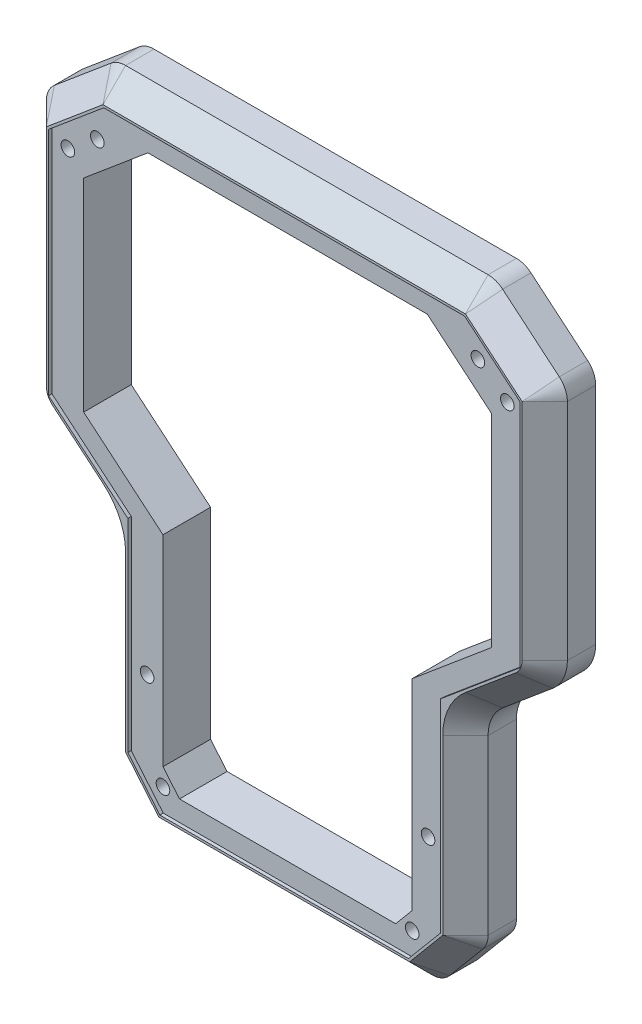
SolidWorks part; units mm, degrees
ref_plane "Plano frontal" through (0, 0, 0) normal (0, 0, 1) x (1, 0, 0)
ref_plane "Plano superior" through (0, 0, 0) normal (0, 1, 0) x (1, 0, 0)
ref_plane "Plano direito" through (0, 0, 0) normal (1, 0, 0) x (0, 0, -1)
sketch "Esboço1" plane through (0, 0, 0) normal (0, 0, 1) x (1, 0, 0)
  line L0 (-55.3369, 0) -> (55.3369, 0)
  line L1 (-80, 27.4748) -> (-80, 103.8351)
  line L2 (-86.4279, 117.6197) -> (-108.5721, 136.2009)
  line L3 (-115, 149.9856) -> (-115, 249.0225)
  line L4 (-80, 280) -> (80, 280)
  line L5 (0, 280) -> (0, 0) construction
  line L6 (-86.4279, 277.6604) -> (-111.4279, 256.683)
  line L7 (-90, 146.7252) -> (-90, 236.2287)
  line L8 (-90, 236.2287) -> (-61.6704, 260)
  line L9 (47.7197, 20) -> (-47.7197, 20)
  line L10 (-55, 28.6763) -> (-55, 117.3567)
  line L11 (-55, 117.3567) -> (-90, 146.7252)
  line L12 (-77.6604, 21.0469) -> (-62.9974, 3.5721)
  line L13 (-55, 28.6763) -> (-47.7197, 20)
  line L14 (-61.6704, 260) -> (61.6704, 260)
  line L15 (55, 28.6763) -> (47.7197, 20)
  line L16 (77.6604, 21.0469) -> (62.9974, 3.5721)
  line L17 (55, 117.3567) -> (90, 146.7252)
  line L18 (55, 28.6763) -> (55, 117.3567)
  line L19 (90, 236.2287) -> (61.6704, 260)
  line L20 (90, 146.7252) -> (90, 236.2287)
  line L21 (86.4279, 277.6604) -> (111.4279, 256.683)
  line L22 (115, 149.9856) -> (115, 249.0225)
  line L23 (86.4279, 117.6197) -> (108.5721, 136.2009)
  line L24 (80, 27.4748) -> (80, 103.8351)
  arc A0 (-115, 249.0225) -> (-111.4279, 256.683) centre (-105, 249.0225) cw
  arc A1 (-108.5721, 136.2009) -> (-115, 149.9856) centre (-97.0055, 149.9856) cw
  arc A2 (-80, 103.8351) -> (-86.4279, 117.6197) centre (-97.9945, 103.8351) ccw
  arc A3 (80, 280) -> (86.4279, 277.6604) centre (80, 270) cw
  arc A4 (-80, 280) -> (-86.4279, 277.6604) centre (-80, 270) ccw
  arc A5 (80, 103.8351) -> (86.4279, 117.6197) centre (97.9945, 103.8351) cw
  arc A6 (108.5721, 136.2009) -> (115, 149.9856) centre (97.0055, 149.9856) ccw
  arc A7 (115, 249.0225) -> (111.4279, 256.683) centre (105, 249.0225) ccw
  arc A8 (77.6604, 21.0469) -> (80, 27.4748) centre (70, 27.4748) ccw
  arc A9 (62.9974, 3.5721) -> (55.3369, 0) centre (55.3369, 10) cw
  arc A10 (-55.3369, 0) -> (-62.9974, 3.5721) centre (-55.3369, 10) cw
  arc A11 (-80, 27.4748) -> (-77.6604, 21.0469) centre (-70, 27.4748) ccw
  point P27 (-115, 253.6856)
  point P33 (0, 20)
  point P40 (0, 260)
  point P46 (0, 20)
  point P47 (115, 253.6856)
  point P50 (80, 23.8351)
  point P53 (0, 280)
  point P54 (60, 0)
  point P57 (-60, 0)
  point P60 (-80, 23.8351)
  dimension "D7" = 50
  dimension "D12" = 10
  dimension "D14" = 10
  dimension "D19" = 10
  dimension "D2" = 115
  dimension "D3" = 280
  dimension "D4" = 80
  dimension "D5" = 80
  dimension "D6" = 50
  dimension "D8" = 20
  dimension "D9" = 20
  dimension "D10" = 25
  dimension "D11" = 20
  dimension "D13" = 50
  dimension "D15" = 25
  dimension "D16" = 50
  dimension "D17" = 60
  dimension "D18" = 50
extrude "Ressalto-extrusão1" add sketch "Esboço1" along normal mid plane 45 contours L5 L4 L6 L3 A1 L2 A2 L1 L12 L0 L10 L11 L14 | L4 L5 L14 L0 region at (-58.2839, 3.6803, 0) region at (3.027, 10, 0)
chamfer "Chanfro1" distance 10 angle 45 48 edges at (0, 0, 22.5) (-70.3289, 12.3095, 22.5) (-80, 65.6549, 22.5) (-81.6859, 111.4399, 22.5) (-97.5, 126.9103, 22.5) (0, 280, 22.5) (-113.3141, 142.3807, 22.5) (-98.9279, 267.1717, 22.5) (-115, 199.504, 22.5) (0, 0, -22.5) (-70.3289, 12.3095, -22.5) (-80, 65.6549, -22.5) (-81.6859, 111.4399, -22.5) (-97.5, 126.9103, -22.5) (0, 280, -22.5) (-113.3141, 142.3807, -22.5) (-98.9279, 267.1717, -22.5) (-115, 199.504, -22.5) (80, 65.6549, 22.5) (81.6859, 111.4399, 22.5) (97.5, 126.9103, 22.5) (113.3141, 142.3807, 22.5) (115, 199.504, 22.5) (114.0631, 253.2487, 22.5) (98.9279, 267.1717, 22.5) (83.4202, 279.3969, 22.5) (-83.4202, 279.3969, 22.5) (-114.0631, 253.2487, 22.5) (80, 65.6549, -22.5) (81.6859, 111.4399, -22.5) (97.5, 126.9103, -22.5) (113.3141, 142.3807, -22.5) (115, 199.504, -22.5) (114.0631, 253.2487, -22.5) (98.9279, 267.1717, -22.5) (83.4202, 279.3969, -22.5) (-83.4202, 279.3969, -22.5) (-114.0631, 253.2487, -22.5) (70.3289, 12.3095, -22.5) (70.3289, 12.3095, 22.5) (79.3969, 24.0546, 22.5) (59.5631, 0.9369, 22.5) (-59.5631, 0.9369, 22.5) (-79.3969, 24.0546, 22.5) (79.3969, 24.0546, -22.5) (59.5631, 0.9369, -22.5) (-59.5631, 0.9369, -22.5) (-79.3969, 24.0546, -22.5)
sketch "Esboço3" plane through (0, 0, 0) normal (0, 0, 1) x (1, 0, 0)
  line L1 (-722.7729, 507.4347) -> (416.458, 507.4347)
  line L2 (-722.7729, 507.4347) -> (-722.7729, -202.3634)
  line L3 (-722.7729, -202.3634) -> (416.458, -202.3634)
  line L4 (416.458, 507.4347) -> (416.458, -202.3634)
extrude "Corte-extrusão1" cut sketch "Esboço3" against normal up to next
sketch "Esboço4" plane through (0, 0, 22.5) normal (0, 0, 1) x (1, 0, 0)
  line L0 (-90, 146.7252) -> (-90, 236.2287)
  line L1 (-55, 117.3567) -> (-90, 146.7252)
  line L2 (-55, 117.3567) -> (-90, 146.7252) construction
  line L3 (-55, 28.6763) -> (-55, 117.3567)
  line L4 (-55, 28.6763) -> (-47.7197, 20)
  line L5 (0, -6.7811) -> (0, 343.2781) construction
  line L6 (-47.7197, 20) -> (47.7197, 20)
  line L7 (55, 28.6763) -> (47.7197, 20)
  line L8 (-69, 27.8387) -> (-54.8706, 11)
  line L9 (-54.8706, 11) -> (54.8706, 11)
  line L10 (90, 236.2287) -> (61.6704, 260) construction
  line L11 (-90, 236.2287) -> (-61.6704, 260)
  line L12 (-61.6704, 260) -> (61.6704, 260)
  line L13 (-104, 248.5562) -> (-79.636, 269)
  line L14 (-104, 248.5562) -> (-104, 146.7239)
  line L15 (-104, 146.7239) -> (-69, 117.3555)
  line L16 (-69, 117.3555) -> (-69, 27.8387)
  line L17 (54.8706, 11) -> (69, 27.8387)
  line L18 (61.6704, 260) -> (90, 236.2287)
  line L19 (-79.636, 269) -> (79.636, 269)
  line L20 (69, 117.3555) -> (69, 27.8387)
  line L21 (104, 146.7239) -> (69, 117.3555)
  line L22 (104, 248.5562) -> (104, 146.7239)
  line L23 (-70, 27.4748) -> (-55.3369, 10) construction
  line L24 (55, 28.6763) -> (55, 117.3567)
  line L25 (55, 117.3567) -> (90, 146.7252)
  line L26 (90, 236.2287) -> (90, 146.7252)
  line L27 (79.636, 269) -> (104, 248.5562)
  line L28 (-80, 270) -> (-105, 249.0225) construction
  line L29 (105, 249.0225) -> (80, 270) construction
  line L30 (55.3369, 10) -> (70, 27.4748) construction
  dimension "D1" = 14
  dimension "D2" = 9
  dimension "D3" = 9
  dimension "D4" = 14
  dimension "D5" = 9
  dimension "D6" = 1
  dimension "D7" = 1
extrude "Corte-extrusão5" cut sketch "Esboço4" against normal blind 1.5
sketch "Esboço5" plane through (0, 0, 21) normal (0, 0, 1) x (1, 0, 0)
  line L1 (-104, 248.5562) -> (-104, 146.7239) construction
  line L2 (-69, 117.3555) -> (-69, 27.8387) construction
  line L3 (0, -34.4878) -> (0, 335.3959) construction
  line L5 (-104, 248.5562) -> (-104, 146.7239) construction
  line L7 (79.636, 269) -> (-79.636, 269) construction
  line L8 (-69, 117.3555) -> (-69, 27.8387) construction
  line L9 (-54.8706, 11) -> (54.8706, 11) construction
  circle A0 centre (-97, 244) radius 3
  circle A1 centre (-62, 60.3962) radius 3
  circle A2 centre (-84, 254) radius 3
  circle A3 centre (-55, 21) radius 3
  circle A4 centre (55, 21) radius 3
  circle A5 centre (84, 254) radius 3
  circle A6 centre (62, 60.3962) radius 3
  circle A7 centre (97, 244) radius 3
  dimension "D1" = 15
  dimension "D3" = 7
  dimension "D4" = 14
  dimension "D5" = 20
  dimension "D6" = 10
  dimension "D2" = 7
extrude "Corte-extrusão6" cut sketch "Esboço5" against normal through all
sketch "Esboço7" plane through (0, 0, 0) normal (0, 0, -1) x (-1, 0, 0)
  line L1 (83.8624, 258.0391) -> (80.4332, 255.9004)
  line L2 (80.4332, 255.9004) -> (80.5708, 251.8613)
  line L3 (80.5708, 251.8613) -> (84.1376, 249.9609)
  line L4 (84.1376, 249.9609) -> (87.5668, 252.0996)
  line L5 (87.5668, 252.0996) -> (87.4292, 256.1387)
  line L6 (87.4292, 256.1387) -> (83.8624, 258.0391)
  line L7 (-96.7313, 248.0325) -> (-100.3579, 246.2489)
  line L8 (-100.3579, 246.2489) -> (-100.6266, 242.2164)
  line L9 (-100.6266, 242.2164) -> (-97.2687, 239.9675)
  line L10 (-97.2687, 239.9675) -> (-93.6421, 241.7511)
  line L11 (-93.6421, 241.7511) -> (-93.3734, 245.7836)
  line L12 (-93.3734, 245.7836) -> (-96.7313, 248.0325)
  line L13 (-62, 64.4377) -> (-65.5, 62.417)
  line L14 (-65.5, 62.417) -> (-65.5, 58.3755)
  line L15 (-65.5, 58.3755) -> (-62, 56.3548)
  line L16 (-62, 56.3548) -> (-58.5, 58.3755)
  line L17 (-58.5, 58.3755) -> (-58.5, 62.417)
  line L18 (-58.5, 62.417) -> (-62, 64.4377)
  line L19 (-84, 258.0415) -> (-87.5, 256.0207)
  line L20 (-87.5, 256.0207) -> (-87.5, 251.9793)
  line L21 (-87.5, 251.9793) -> (-84, 249.9585)
  line L22 (-84, 249.9585) -> (-80.5, 251.9793)
  line L23 (-80.5, 251.9793) -> (-80.5, 256.0207)
  line L24 (-80.5, 256.0207) -> (-84, 258.0415)
  line L25 (54.7616, 25.0344) -> (51.3869, 22.8108)
  line L26 (51.3869, 22.8108) -> (51.6253, 18.7764)
  line L27 (51.6253, 18.7764) -> (55.2384, 16.9656)
  line L28 (55.2384, 16.9656) -> (58.6131, 19.1892)
  line L29 (58.6131, 19.1892) -> (58.3747, 23.2236)
  line L30 (58.3747, 23.2236) -> (54.7616, 25.0344)
  line L31 (62, 64.4377) -> (58.5, 62.417)
  line L32 (58.5, 62.417) -> (58.5, 58.3755)
  line L33 (58.5, 58.3755) -> (62, 56.3548)
  line L34 (62, 56.3548) -> (65.5, 58.3755)
  line L35 (65.5, 58.3755) -> (65.5, 62.417)
  line L36 (65.5, 62.417) -> (62, 64.4377)
  line L37 (97, 248.0415) -> (93.5, 246.0207)
  line L38 (93.5, 246.0207) -> (93.5, 241.9793)
  line L39 (93.5, 241.9793) -> (97, 239.9585)
  line L40 (97, 239.9585) -> (100.5, 241.9793)
  line L41 (100.5, 241.9793) -> (100.5, 246.0207)
  line L42 (100.5, 246.0207) -> (97, 248.0415)
  line L43 (-55.3342, 25.0276) -> (-58.6551, 22.7244)
  line L44 (-58.6551, 22.7244) -> (-58.3209, 18.6968)
  line L45 (-58.3209, 18.6968) -> (-54.6658, 16.9724)
  line L46 (-54.6658, 16.9724) -> (-51.3449, 19.2756)
  line L47 (-51.3449, 19.2756) -> (-51.6791, 23.3032)
  line L48 (-51.6791, 23.3032) -> (-55.3342, 25.0276)
  circle A0 centre (84, 254) radius 3.5 construction
  circle A1 centre (-97, 244) radius 3.5 construction
  circle A2 centre (-62, 60.3962) radius 3.5 construction
  circle A3 centre (-84, 254) radius 3.5 construction
  circle A4 centre (55, 21) radius 3.5 construction
  circle A5 centre (62, 60.3962) radius 3.5 construction
  circle A6 centre (97, 244) radius 3.5 construction
  circle A7 centre (-55, 21) radius 3.5 construction
extrude "Corte-extrusão8" cut sketch "Esboço7" against normal blind 10
